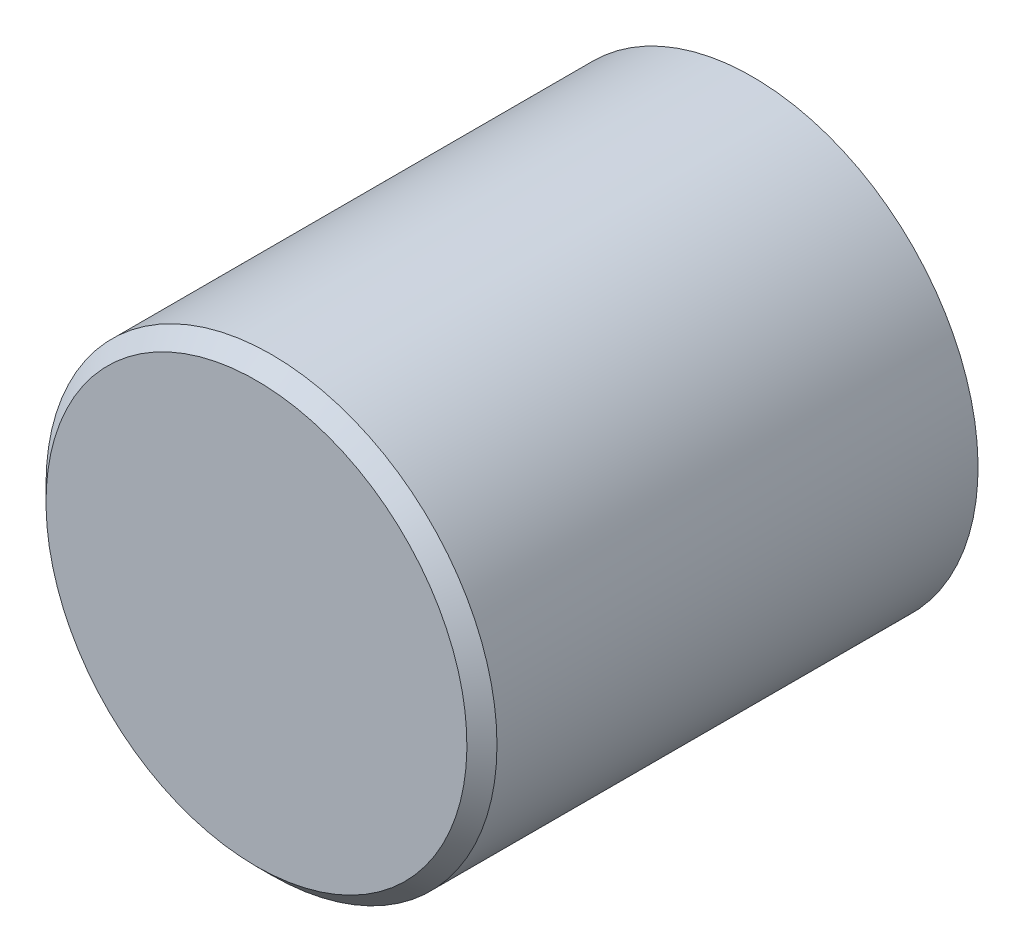
SolidWorks part; units mm, degrees
note: The reader was unsure of these and kept them because the rebuilt part matched: shared geometry of "Sketch1<3>".
ref_plane "Front Plane" through (0, 0, 0) normal (0, 0, 1) x (1, 0, 0)
ref_plane "Top Plane" through (0, 0, 0) normal (0, 1, 0) x (1, 0, 0)
ref_plane "Right Plane" through (0, 0, 0) normal (1, 0, 0) x (0, 0, -1)
sketch "Sketch1" plane through (0, 0, 0) normal (0, 0, 1) x (1, 0, 0)
  line L1 (5.2763, 10.2466) -> (5.2763, 5.7567)
  line L2 (5.2763, 10.2466) -> (5.2763, 5.7567) construction
  arc A0 (5.2763, 5.7567) -> (6.7763, 5.3016) centre (6.7763, 8.0016) ccw
  arc A1 (6.7763, 5.3016) -> (6.7763, 10.7016) centre (6.7763, 8.0016) ccw
  arc A2 (6.7763, 10.7016) -> (5.2763, 10.2466) centre (6.7763, 8.0016) ccw
  arc A3 (5.2763, 5.7567) -> (6.7763, 5.3016) centre (6.7763, 8.0016) ccw construction
  arc A4 (6.7763, 5.3016) -> (6.7763, 10.7016) centre (6.7763, 8.0016) ccw construction
  arc A5 (6.7763, 10.7016) -> (5.2763, 10.2466) centre (6.7763, 8.0016) ccw construction
  circle A6 centre (6.7763, 8.0016) radius 7.5
  circle A7 centre (6.7763, 8.0016) radius 3
  dimension "D2" = 15
  dimension "D3" = 6
  dimension "D1" = 0
ref_plane "top offset plane" through (0, 0, 8.875) normal (0, 0, 1) x (1, 0, 0)
extrude "extrude knob" add sketch "Sketch1" along normal blind 16.5 from surface at 8.875 contours A6 A7 starting at plane "top offset plane"
extrude "extrude knob inner" add sketch "Sketch1<3>" against normal blind 1 from surface at 25.375 contours A7 starting at face at (6.7763, 0.5016, 25.375)
sketch "Sketch1<3>" plane through (0, 0, 0) normal (0, 0, 1) x (1, 0, 0) same geometry as "Sketch1"
chamfer "chamfer knob" distance 0.5 angle 45 1 edges at (6.7763, 0.5016, 25.375)
